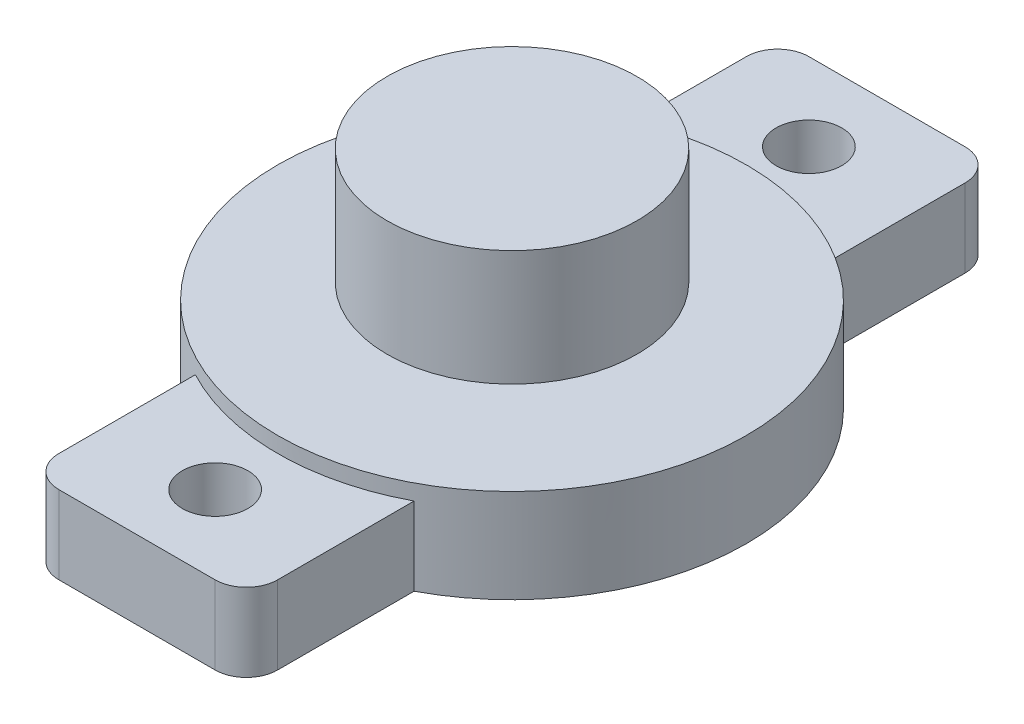
SolidWorks part; units mm, degrees
ref_plane "Front Plane" through (0, 0, 0) normal (0, 0, 1) x (1, 0, 0)
ref_plane "Top Plane" through (0, 0, 0) normal (0, 1, 0) x (1, 0, 0)
ref_plane "Right Plane" through (0, 0, 0) normal (1, 0, 0) x (0, 0, -1)
sketch "Sketch1" plane through (0, 0, 0) normal (0, 1, 0) x (1, 0, 0)
  line L1 (-3.5, -12) -> (3.5, -12)
  line L2 (-3.5, -12) -> (-3.5, 12)
  line L3 (-3.5, 12) -> (3.5, 12)
  line L4 (3.5, -12) -> (3.5, 12)
  line L5 (-3.5, -12) -> (3.5, 12) construction
  line L6 (-3.5, 12) -> (3.5, -12) construction
  point P0 (0, 0)
  dimension "D1" = 24
  dimension "D2" = 7
extrude "Boss-Extrude1" add sketch "Sketch1" along normal blind 2.5
fillet "Fillet1" radius 1 4 edges at (3.5, 1.25, -12) (-3.5, 1.25, -12) (3.5, 1.25, 12) (-3.5, 1.25, 12)
sketch "Sketch2" plane through (0, 2.5, 0) normal (0, 1, 0) x (1, 0, 0)
  circle A0 centre (0, 0) radius 7.5
  dimension "D1" = 15
extrude "Boss-Extrude2" add sketch "Sketch2" against normal up to surface (2.5 mm away) and the other way blind 0.5 up to face at (0, 0, 0)
sketch "Sketch3" plane through (0, 2.5, 0) normal (0, 1, 0) x (1, 0, 0)
  line L0 (0, 9.5) -> (0, -9.5) construction
  circle A0 centre (0, 9.5) radius 1.05
  circle A1 centre (0, -9.5) radius 1.05
  point P3 (0, 0)
  dimension "D2" = 2.1
  dimension "D1" = 19
extrude "Cut-Extrude1" cut sketch "Sketch3" against normal blind 22.5
sketch "Sketch5" plane through (0, 3, 0) normal (0, 1, 0) x (1, 0, 0)
  circle A0 centre (0, 0) radius 1.5612
extrude "Boss-Extrude3" add sketch "Sketch5" along normal blind 0.5
sketch "Sketch6" plane through (0, 3.5, 0) normal (0, 1, 0) x (1, 0, 0)
  circle A0 centre (0, 0) radius 4
  dimension "D1" = 8
extrude "Boss-Extrude4" add sketch "Sketch6" along normal blind 3.7
